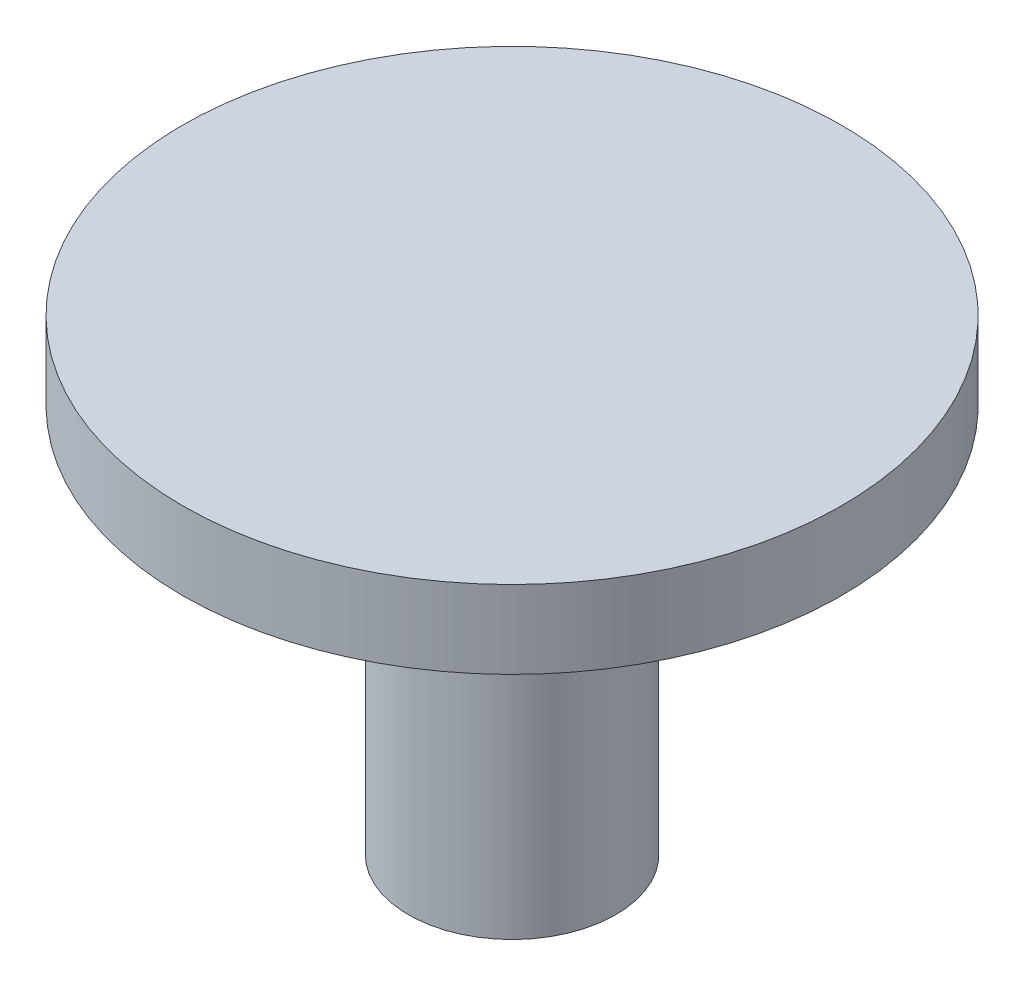
SolidWorks part; units mm, degrees
ref_plane "Alzado" through (0, 0, 0) normal (0, 0, 1) x (1, 0, 0)
ref_plane "Planta" through (0, 0, 0) normal (0, 1, 0) x (1, 0, 0)
ref_plane "Vista lateral" through (0, 0, 0) normal (1, 0, 0) x (0, 0, -1)
sketch "Croquis1" plane through (0, 0, 0) normal (0, 1, 0) x (1, 0, 0)
  circle A0 centre (0, 0) radius 12.7
  dimension "D1" = 25.4
extrude "Saliente-Extruir1" add sketch "Croquis1" along normal blind 3
sketch "Croquis2" plane through (0, 0, 0) normal (0, -1, 0) x (1, 0, 0)
  circle A0 centre (0, 0) radius 4
  dimension "D1" = 8
extrude "Saliente-Extruir2" add sketch "Croquis2" along normal blind 15
sketch "Croquis3" plane through (0, 0, 0) normal (0, -1, 0) x (-1, 0, 0)
  line L0 (1.1045, 3.8445) -> (3.5068, 12.2063)
  circle A0 centre (0, 0) radius 4 construction
  circle A1 centre (0, 0) radius 12.7 construction
